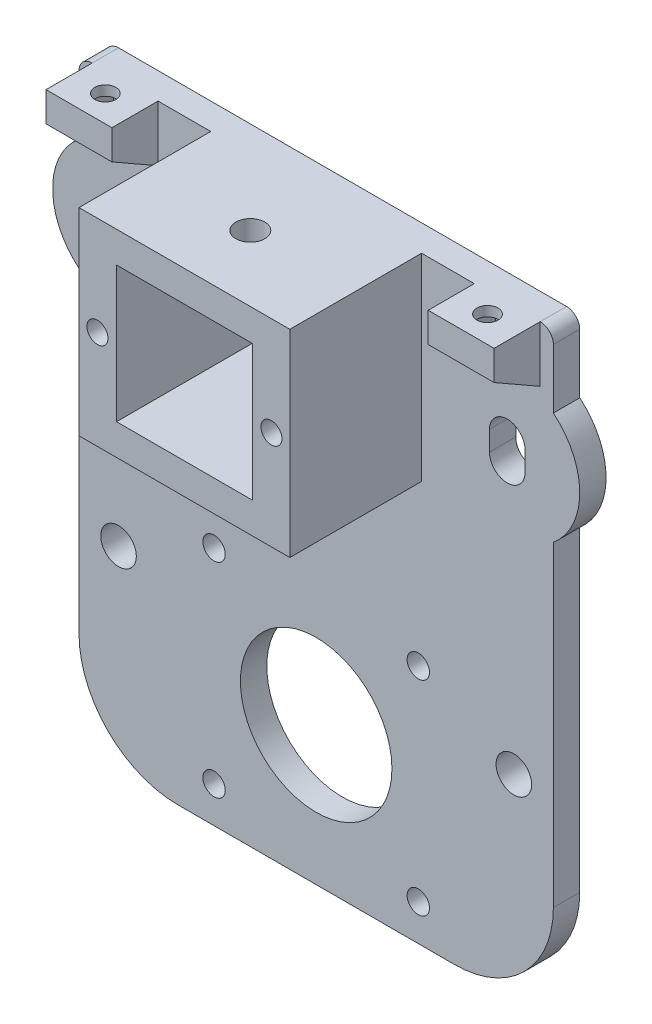
SolidWorks part; units mm, degrees
note: The reader was unsure of these and kept them because the rebuilt part matched: shared geometry of "草图1<3>", "草图1<4>".
ref_plane "前视基准面" through (0, 0, 0) normal (0, 0, 1) x (1, 0, 0)
ref_plane "上视基准面" through (0, 0, 0) normal (0, 1, 0) x (1, 0, 0)
ref_plane "右视基准面" through (0, 0, 0) normal (1, 0, 0) x (0, 0, -1)
sketch "草图1" plane through (0, 0, 0) normal (0, 0, 1) x (1, 0, 0)
  line L0 (-1000, 0) -> (49000, 0) construction
  line L1 (-973.7065, 20) -> (49026.2935, 20) construction
  line L2 (-972.6802, 10) -> (49027.3198, 10) construction
  line L3 (0, -1000) -> (0, 49000) construction
  line L4 (-29, -970.2065) -> (-29, 49029.7935) construction
  line L5 (-10.3, 25.2) -> (10.3, 25.2)
  line L6 (-10.3, 25.2) -> (-10.3, 45.8)
  line L7 (-10.3, 45.8) -> (10.3, 45.8)
  line L8 (10.3, 25.2) -> (10.3, 45.8)
  line L9 (-10.3, 25.2) -> (10.3, 45.8) construction
  line L10 (-10.3, 45.8) -> (10.3, 25.2) construction
  line L11 (-21, 1.5) -> (21, 1.5)
  line L12 (-21, 1.5) -> (-21, -40.5)
  line L13 (-21, -40.5) -> (21, -40.5)
  line L14 (21, 1.5) -> (21, -40.5)
  line L15 (-21, 1.5) -> (21, -40.5) construction
  line L16 (-21, -40.5) -> (21, 1.5) construction
  line L17 (-16, 20.5) -> (16, 20.5)
  line L18 (-16, 20.5) -> (-16, 50.5)
  line L19 (-16, 50.5) -> (16, 50.5)
  line L20 (16, 20.5) -> (16, 50.5)
  line L21 (-16, 20.5) -> (16, 50.5) construction
  line L22 (-16, 50.5) -> (16, 20.5) construction
  line L23 (-34, 50.5) -> (34, 50.5)
  line L24 (-36, 48.5) -> (-36, -25.5)
  line L25 (-21, -40.5) -> (21, -40.5)
  line L26 (36, 48.5) -> (36, -25.5)
  line L27 (-34, 50.5) -> (-24, 50.5)
  line L28 (-34, 50.5) -> (-34, 46)
  line L29 (-34, 46) -> (-24, 46)
  line L30 (-24, 50.5) -> (-24, 46)
  line L31 (-29, 32.5) -> (-29, 29.5) construction
  line L32 (-26.3, 32.5) -> (-26.3, 29.5)
  line L33 (-31.7, 32.5) -> (-31.7, 29.5)
  line L34 (29, 32.5) -> (29, 29.5) construction
  line L35 (34, 50.5) -> (34, 46)
  line L36 (34, 50.5) -> (24, 50.5)
  line L37 (24, 50.5) -> (24, 46)
  line L38 (34, 46) -> (24, 46)
  line L39 (31.7, 32.5) -> (31.7, 29.5)
  line L40 (26.3, 32.5) -> (26.3, 29.5)
  circle A0 centre (0, -19.5) radius 11.5
  circle A1 centre (15.5, -4) radius 1.7
  circle A2 centre (15.5, -35) radius 1.7
  circle A3 centre (-15.5, -35) radius 1.7
  circle A4 centre (-15.5, -4) radius 1.7
  circle A5 centre (-15.5, -4) radius 4 construction
  circle A6 centre (-30, -11) radius 11
  circle A7 centre (-30, -11) radius 2.7
  circle A8 centre (-30, -11) radius 5 construction
  circle A9 centre (30, -11) radius 2.7
  circle A10 centre (30, -11) radius 5 construction
  circle A11 centre (30, -11) radius 11
  circle A12 centre (-29, 31) radius 5 construction
  circle A13 centre (-29, 31) radius 2.7 construction
  circle A14 centre (-29, 31) radius 11
  circle A15 centre (29, 31) radius 5 construction
  circle A16 centre (29, 31) radius 11
  circle A17 centre (29, 31) radius 2.7 construction
  arc A18 (-36, -25.5) -> (-21, -40.5) centre (-21, -25.5) ccw
  arc A19 (36, -25.5) -> (21, -40.5) centre (21, -25.5) cw
  arc A20 (34, 50.5) -> (36, 48.5) centre (34, 48.5) cw
  arc A21 (-34, 50.5) -> (-36, 48.5) centre (-34, 48.5) ccw
  arc A22 (-26.3, 32.5) -> (-31.7, 32.5) centre (-29, 32.5) ccw
  arc A23 (-31.7, 29.5) -> (-26.3, 29.5) centre (-29, 29.5) ccw
  arc A24 (31.7, 32.5) -> (26.3, 32.5) centre (29, 32.5) ccw
  arc A25 (26.3, 29.5) -> (31.7, 29.5) centre (29, 29.5) ccw
  circle A26 centre (13.2, 35.5) radius 1.6
  circle A27 centre (-13.2, 35.5) radius 1.6
  circle A28 centre (29, 31) radius 12 construction
  point P8 (0, 35.5)
  point P14 (0, -19.5)
  point P32 (0, -19.5)
  point P35 (0, 35.5)
  point P72 (-29, 31)
  point P83 (29, 31)
  dimension "D7" = 23
  dimension "D8" = 3.4
  dimension "D11" = 8
  dimension "D12" = 22
  dimension "D13" = 5.4
  dimension "D14" = 10
  dimension "D19" = 22
  dimension "D18" = 10
  dimension "D20" = 5.4
  dimension "D23" = 2
  dimension "D26" = 2.7
  dimension "D29" = 3.2
  dimension "D31" = 24
  dimension "D32" = 15
  dimension "D33" = 15
  dimension "D1" = 10
  dimension "D2" = 10
  dimension "D3" = 20.6
  dimension "D4" = 20.6
  dimension "D5" = 42
  dimension "D6" = 42
  dimension "D10" = 31
  dimension "D15" = 32
  dimension "D16" = 30
  dimension "D17" = 60
  dimension "D21" = 58
  dimension "D22" = 6
  dimension "D24" = 10
  dimension "D25" = 4.5
  dimension "D27" = 3
  dimension "D28" = 1
  dimension "D30" = 2.8
  dimension "D9" = 4
extrude "凸台-拉伸1" add sketch "草图1" along normal blind 4
extrude "凸台-拉伸2" add sketch "草图1<3>" along normal blind 7 from offset 4 contours L38 A16 | L29 L30 L27 L28
sketch "草图1<3>" plane through (0, 0, 0) normal (0, 0, 1) x (1, 0, 0) same geometry as "草图1"
extrude "凸台-拉伸3" add sketch "草图1<4>" along normal blind 20 from surface at 4 contours L17 L20 L19 L18 L8 L5 L6 L7
sketch "草图1<4>" plane through (0, 0, 0) normal (0, 0, 1) x (1, 0, 0) same geometry as "草图1"
sketch "草图3" plane through (-34, 0, 0) normal (-1, 0, 0) x (0, 0, 1)
  line L1 (11, 46) -> (4, 42)
  line L3 (4, 50.5) -> (4, 20.5) construction
  line L4 (11, 46) -> (4, 46) construction
  dimension "D1" = 4
rib "筋1" sketch "草图3" sketch "草图3" thickness 1.7 extrusion direction parallel to sketch draft on no parameters "D1"=1.7
sketch "草图4" plane through (-24, 0, 0) normal (1, 0, 0) x (0, 0, -1)
  line L0 (-11, 46) -> (-4, 42) construction
  line L1 (-11, 46) -> (-4, 42)
rib "筋2" sketch "草图4" sketch "草图4" thickness 1.7 extrusion direction parallel to sketch draft on no parameters "D1"=1.7
mirror "镜向1" about plane through (0, 0, 0) normal (1, 0, 0) of "筋2", "筋1"
sketch "草图5" plane through (0, 50.5, 0) normal (0, 1, 0) x (1, 0, 0)
  line L0 (16, -4) -> (24, -4) construction
  line L1 (0, 0) -> (0, -14) construction
  circle A0 centre (0, -14) radius 2.2
  circle A1 centre (29, -7) radius 1.6
  circle A2 centre (29, -7) radius 3 construction
  circle A3 centre (-29, -7) radius 1.6
  dimension "D1" = 4.4
  dimension "D3" = 3.2
  dimension "D4" = 6
  dimension "D2" = 14
  dimension "D5" = 5
extrude "切除-拉伸1" cut sketch "草图5" against normal up to next
sketch "草图6" plane through (0, 46, 0) normal (0, -1, 0) x (1, 0, 0)
  line L1 (-27.3257, 9.9) -> (-30.6743, 9.9)
  line L2 (-30.6743, 9.9) -> (-32.3486, 7)
  line L3 (-32.3486, 7) -> (-30.6743, 4.1)
  line L4 (-30.6743, 4.1) -> (-27.3257, 4.1)
  line L5 (-27.3257, 4.1) -> (-25.6514, 7)
  line L6 (-25.6514, 7) -> (-27.3257, 9.9)
  line L7 (32.3486, 7) -> (30.6743, 9.9)
  line L8 (30.6743, 9.9) -> (27.3257, 9.9)
  line L9 (27.3257, 9.9) -> (25.6514, 7)
  line L10 (25.6514, 7) -> (27.3257, 4.1)
  line L11 (27.3257, 4.1) -> (30.6743, 4.1)
  line L12 (30.6743, 4.1) -> (32.3486, 7)
  circle A0 centre (-29, 7) radius 2.9 construction
  circle A1 centre (29, 7) radius 2.9 construction
  dimension "D1" = 5.8
  dimension "D2" = 5.8
extrude "切除-拉伸2" cut sketch "草图6" against normal blind 3
